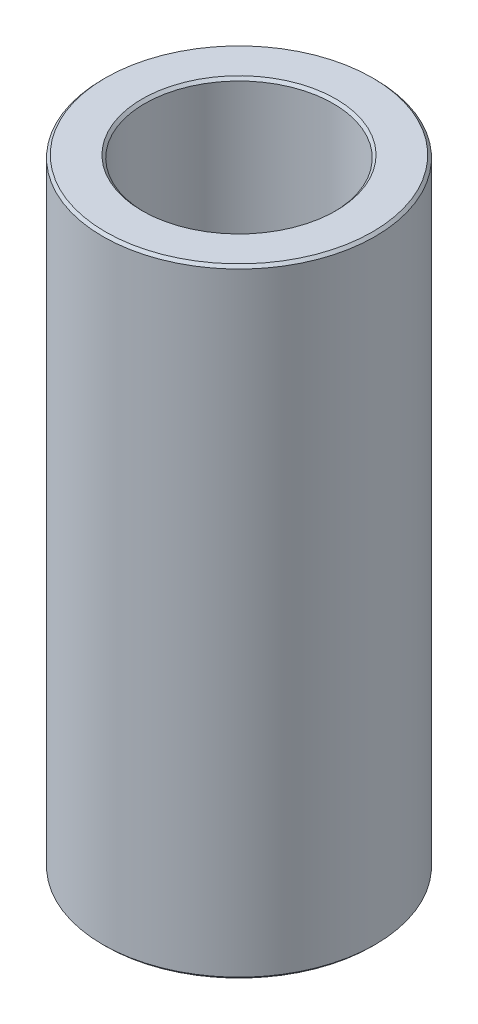
SolidWorks part; units mm, degrees
ref_plane "Front Plane" through (0, 0, 0) normal (0, 0, 1) x (1, 0, 0)
ref_plane "Top Plane" through (0, 0, 0) normal (0, 1, 0) x (1, 0, 0)
ref_plane "Right Plane" through (0, 0, 0) normal (1, 0, 0) x (0, 0, -1)
sketch "Sketch1" plane through (0, 0, 0) normal (0, 1, 0) x (1, 0, 0)
  circle A0 centre (0, 0) radius 35
  dimension "SLEEVE_OD" = 70
extrude "Boss-Extrude1" add sketch "Sketch1" along normal blind 159.0385
sketch "Sketch2" plane through (0, 0, 0) normal (0, 1, 0) x (1, 0, 0)
  circle A0 centre (0, 0) radius 24.2339
  dimension "BORE_D" = 48.4678
extrude "Cut-Extrude1" cut sketch "Sketch2" along normal through all
chamfer "Chamfer1" distance 0.6859 angle 45 4 edges at (0, 159.0385, 24.2339) (0, 0, 24.2339) (0, 0, 35) (0, 159.0385, 35)
